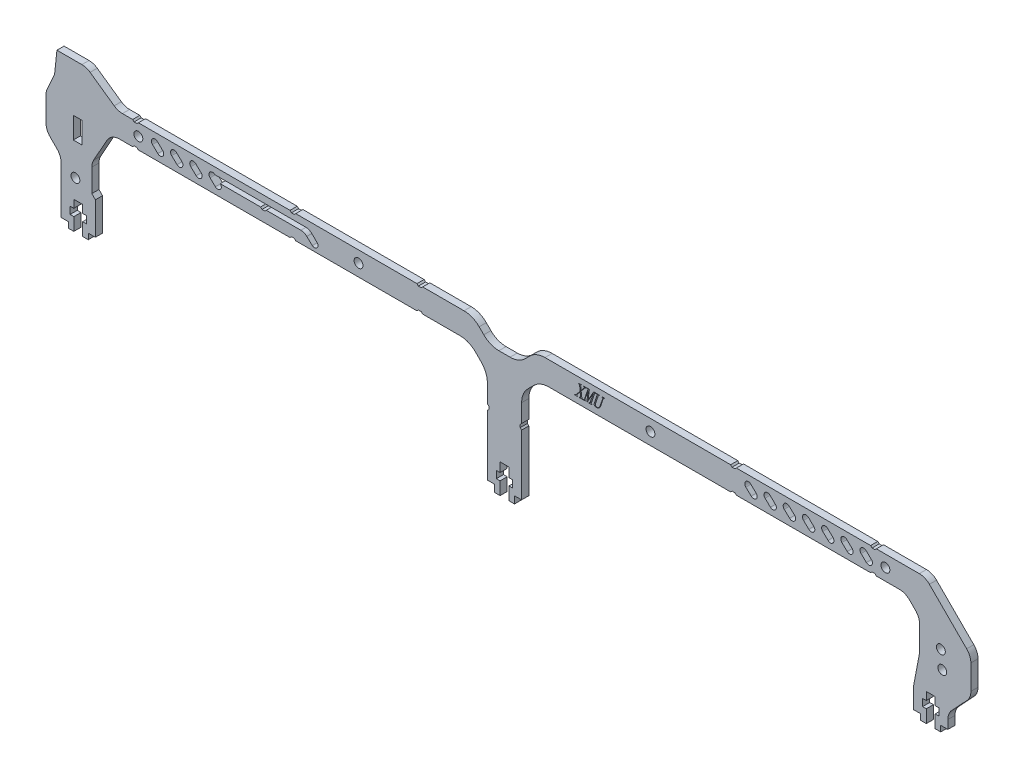
SolidWorks part; units mm, degrees
material "PPS"
ref_plane "前视基准面" through (0, 0, 0) normal (0, 0, 1) x (1, 0, 0)
ref_plane "上视基准面" through (0, 0, 0) normal (0, 1, 0) x (1, 0, 0)
ref_plane "右视基准面" through (0, 0, 0) normal (1, 0, 0) x (0, 0, -1)
sketch "草图1" plane through (0, 0, 0) normal (0, 0, 1) x (1, 0, 0)
  line L0 (-1000, 0) -> (49000, 0) construction
  line L1 (0, 0) -> (0, -218.3822) construction
  line L2 (6, -16.1697) -> (6, -48.75)
  line L3 (6, -48.75) -> (-6, -48.75) construction
  line L4 (-6, -16.1697) -> (-6, -48.75)
  line L5 (6, -48.75) -> (3.5, -48.75)
  line L6 (3.5, -48.75) -> (3.5, -51.25)
  line L7 (3.5, -51.25) -> (-3.5, -51.25) construction
  line L8 (-3.5, -48.75) -> (-3.5, -51.25)
  line L9 (-3.5, -48.75) -> (-6, -48.75)
  line L10 (1.55, -51.25) -> (1.55, -46.75)
  line L11 (1.55, -46.75) -> (2.85, -46.75)
  line L12 (2.85, -46.75) -> (2.85, -44.25)
  line L13 (2.85, -44.25) -> (1.55, -44.25)
  line L14 (1.55, -44.25) -> (1.55, -41)
  line L15 (1.55, -41) -> (-1.55, -41)
  line L16 (-1.55, -44.25) -> (-1.55, -41)
  line L17 (-2.85, -44.25) -> (-1.55, -44.25)
  line L18 (-2.85, -46.75) -> (-2.85, -44.25)
  line L19 (-1.55, -46.75) -> (-2.85, -46.75)
  line L20 (-1.55, -51.25) -> (-1.55, -46.75)
  line L21 (1.55, -51.25) -> (3.5, -51.25)
  line L22 (-1.55, -51.25) -> (-3.5, -51.25)
  line L23 (12.4197, -9.75) -> (6, -16.1697)
  line L24 (-12.4197, -9.75) -> (-6, -16.1697)
  line L25 (-147.7, -45.75) -> (-147.7, -41.25)
  line L26 (-150.8, -45.75) -> (-150.8, -41.25)
  line L27 (-147.7, -41.25) -> (-146.4, -41.25)
  line L28 (-146.4, -41.25) -> (-146.4, -38.75)
  line L29 (-146.4, -38.75) -> (-147.7, -38.75)
  line L30 (-147.7, -38.75) -> (-147.7, -36)
  line L31 (-150.8, -36) -> (-147.7, -36)
  line L32 (-150.8, -38.75) -> (-150.8, -36)
  line L33 (-152.1, -38.75) -> (-150.8, -38.75)
  line L34 (-152.1, -41.25) -> (-152.1, -38.75)
  line L35 (-150.8, -41.25) -> (-152.1, -41.25)
  line L36 (-5.0685, -7.5) -> (5.0685, -7.5)
  line L37 (5.0685, -7.5) -> (11.0685, -1.5)
  line L38 (11.0685, -1.5) -> (147.3211, -1.5)
  line L40 (145.3337, -25.5065) -> (145.3337, -14.709)
  line L41 (140.3747, -9.75) -> (12.4197, -9.75)
  line L42 (-5.0685, -7.5) -> (-11.0685, -1.5)
  line L44 (-11.0685, -1.5) -> (-157.5351, -1.5) construction
  line L45 (-137.7768, -9.75) -> (-12.4197, -9.75)
  line L50 (143.25, -36.4306) -> (143.25, -43.75)
  line L52 (155.25, -43.75) -> (143.25, -43.75) construction
  line L53 (155.25, -43.75) -> (152.75, -43.75)
  line L54 (152.75, -43.75) -> (152.75, -45.75)
  line L55 (152.75, -45.75) -> (145.75, -45.75) construction
  line L56 (145.75, -43.75) -> (145.75, -45.75)
  line L57 (145.75, -43.75) -> (143.25, -43.75)
  line L58 (150.8, -45.75) -> (150.8, -41.25)
  line L59 (150.8, -41.25) -> (152.1, -41.25)
  line L60 (152.1, -41.25) -> (152.1, -38.75)
  line L61 (152.1, -38.75) -> (150.8, -38.75)
  line L62 (150.8, -38.75) -> (150.8, -36)
  line L63 (150.8, -36) -> (147.7, -36)
  line L64 (147.7, -38.75) -> (147.7, -36)
  line L65 (146.4, -38.75) -> (147.7, -38.75)
  line L66 (146.4, -41.25) -> (146.4, -38.75)
  line L67 (147.7, -41.25) -> (146.4, -41.25)
  line L68 (147.7, -45.75) -> (147.7, -41.25)
  line L69 (150.8, -45.75) -> (152.75, -45.75)
  line L70 (147.7, -45.75) -> (145.75, -45.75)
  line L72 (57.6009, -1) -> (44.6221, -1) construction
  line L73 (145.3337, -25.5065) -> (143.25, -36.4306)
  line L74 (-147.7, -45.75) -> (-145.75, -45.75)
  line L75 (-150.8, -45.75) -> (-152.75, -45.75)
  line L76 (-152.75, -43.75) -> (-152.75, -45.75)
  line L77 (-155.25, -43.75) -> (-152.75, -43.75)
  line L78 (-145.75, -43.75) -> (-145.75, -45.75)
  line L79 (-145.75, -43.75) -> (-143.25, -43.75)
  line L80 (-157.5351, -1.5) -> (-160.547, -8.1912)
  line L81 (-160.547, -8.1912) -> (-160.547, -19.809)
  line L82 (-160.547, -19.809) -> (-155.25, -25.0873)
  line L87 (-143.25, -32.3726) -> (-144.5, -31.127)
  line L88 (-144.5, -31.127) -> (-144.5, -21.7902)
  line L89 (-144.5, -21.7902) -> (-137.7768, -9.75)
  line L90 (-155.25, -25.0873) -> (-155.25, -43.75)
  line L91 (-143.25, -32.3726) -> (-143.25, -43.75)
  line L92 (147.3211, -1.5) -> (163.2977, -17.4767)
  line L93 (163.2977, -17.4767) -> (163.2977, -30.1638)
  line L94 (163.2977, -30.1638) -> (155.25, -38.75)
  line L95 (155.25, -38.75) -> (155.25, -43.75)
  line L96 (-157.5351, -1.5) -> (-156.7241, 6.25)
  line L97 (-156.7241, 6.25) -> (-146.4, 6.25)
  line L98 (-146.4, 6.25) -> (-135.37, -1.5)
  line L99 (-135.37, -1.5) -> (-11.0685, -1.5)
  line L102 (140.3747, -9.75) -> (145.3337, -14.709)
  line L103 (56.6009, -9.75) -> (45.6221, -9.75) construction
  line L104 (146.1658, -18.25) -> (92.972, -18.25) construction
  line L105 (-154.7028, -11.25) -> (-130.7962, -11.25) construction
  circle A0 centre (-51.1115, -5.5) radius 1.55
  circle A1 centre (51.1115, -5.5) radius 1.55
  circle A5 centre (-51.1115, -5.5) radius 1.9051 construction
  circle A6 centre (51.1115, -5.5) radius 2.165 construction
  point P6 (0, -48.75)
  point P11 (0, -51.25)
  point P20 (0, -41)
  point P29 (-149.25, -36)
  point P43 (152.75, -44.75)
  point P78 (149.25, -36)
  dimension "D21" = 3.1
  dimension "D1" = 3.5
  dimension "D2" = 4.5
  dimension "D3" = 2.5
  dimension "D4" = 6
  dimension "D5" = 135
  dimension "D6" = 2.5
  dimension "D7" = 48.75
  dimension "D8" = 25.5
  dimension "D9" = 2
  dimension "D10" = 7
  dimension "D11" = 149.25
  dimension "D12" = 1.95
  dimension "D13" = 1.55
  dimension "D14" = 2.85
  dimension "D15" = 10.25
  dimension "D16" = 0.5
  dimension "D17" = 2.25
  dimension "D18" = 135
  dimension "D19" = 135
  dimension "D20" = 1.25
  dimension "D22" = 17.5
extrude "凸台-拉伸1" add sketch "草图1" along normal blind 2.5
sketch "草图2" plane through (0, 0, 0) normal (0, 0, 1) x (1, 0, 0)
  line L0 (98.8244, -4.7341) -> (98.8244, -1.5) construction
  line L2 (147.3211, -1.5) -> (11.0685, -1.5) construction
  line L4 (100.6889, -6.5159) -> (100.6889, -9.75) construction
  line L7 (12.4197, -9.75) -> (140.3747, -9.75) construction
  line L8 (94.8107, -5.6378) -> (97.9607, -5.6378) construction
  line L11 (86.3905, -7.4197) -> (84.526, -5.6378)
  line L16 (121.7047, -5.6122) -> (124.8547, -5.6122) construction
  line L17 (106.5671, -7.394) -> (104.7026, -5.6122)
  line L18 (104.7026, -5.6122) -> (106.4054, -3.8303) construction
  line L19 (106.4054, -3.8303) -> (108.27, -5.6122)
  line L20 (108.27, -5.6122) -> (106.5671, -7.394) construction
  line L21 (99.8252, -7.4197) -> (97.9607, -5.6378)
  line L22 (99.6881, -3.8303) -> (101.5526, -5.6122)
  line L23 (101.5526, -5.6122) -> (104.7026, -5.6122) construction
  line L24 (108.27, -5.6122) -> (111.42, -5.6122) construction
  line L25 (113.2845, -7.394) -> (111.42, -5.6122)
  line L26 (113.1228, -3.8303) -> (114.9873, -5.6122)
  line L27 (114.9873, -5.6122) -> (118.1373, -5.6122) construction
  line L28 (120.0018, -7.394) -> (118.1373, -5.6122)
  line L29 (119.8402, -3.8303) -> (121.7047, -5.6122)
  line L30 (126.7192, -7.394) -> (124.8547, -5.6122)
  line L31 (126.5819, -3.8048) -> (128.4464, -5.5866)
  line L32 (86.2289, -3.856) -> (88.0934, -5.6378)
  line L33 (88.0934, -5.6378) -> (91.2434, -5.6378) construction
  line L34 (93.1079, -7.4197) -> (91.2434, -5.6378)
  line L35 (92.9462, -3.856) -> (94.8107, -5.6378)
  line L36 (-106.2679, -5.6378) -> (-103.1179, -5.6378) construction
  line L38 (-112.9852, -5.6378) -> (-109.8352, -5.6378) construction
  line L39 (-121.4054, -7.4197) -> (-123.27, -5.6378)
  line L42 (-107.9707, -7.4197) -> (-109.8352, -5.6378)
  line L44 (-108.1324, -3.856) -> (-106.2679, -5.6378)
  line L47 (-101.2387, -7.4197) -> (-103.1032, -5.6378)
  line L48 (-101.4003, -3.856) -> (-99.5358, -5.6378) construction
  line L51 (-101.4003, -3.856) -> (-69.6149, -3.856)
  line L56 (-121.5671, -3.856) -> (-119.7026, -5.6378)
  line L57 (-119.7026, -5.6378) -> (-116.5526, -5.6378) construction
  line L58 (-114.6881, -7.4197) -> (-116.5526, -5.6378)
  line L59 (-114.8498, -3.856) -> (-112.9852, -5.6378)
  line L60 (-71.3031, -5.6378) -> (-99.5358, -5.6378)
  line L66 (-67.5422, -4.6871) -> (-65.6228, -6.5214)
  line L69 (-67.311, -8.3033) -> (-69.2304, -6.469)
  arc A10 (126.5819, -3.8048) -> (124.8547, -5.6122) centre (125.7183, -4.7085) ccw
  arc A11 (128.4464, -5.5866) -> (126.7192, -7.394) centre (127.5828, -6.4903) cw
  arc A12 (106.4054, -3.8303) -> (104.7026, -5.6122) centre (105.554, -4.7213) ccw
  arc A13 (108.27, -5.6122) -> (106.5671, -7.394) centre (107.4185, -6.5031) cw
  arc A14 (99.6881, -3.8303) -> (97.9607, -5.6378) centre (98.8244, -4.7341) ccw
  arc A15 (101.5526, -5.6122) -> (99.8252, -7.4197) centre (100.6889, -6.5159) cw
  arc A16 (113.1228, -3.8303) -> (111.42, -5.6122) centre (112.2714, -4.7213) ccw
  arc A17 (114.9873, -5.6122) -> (113.2845, -7.394) centre (114.1359, -6.5031) cw
  arc A18 (119.8402, -3.8303) -> (118.1373, -5.6122) centre (118.9887, -4.7213) ccw
  arc A19 (121.7047, -5.6122) -> (120.0018, -7.394) centre (120.8532, -6.5031) cw
  arc A20 (86.2289, -3.856) -> (84.526, -5.6378) centre (85.3774, -4.7469) ccw
  arc A21 (88.0934, -5.6378) -> (86.3905, -7.4197) centre (87.242, -6.5287) cw
  arc A22 (92.9462, -3.856) -> (91.2434, -5.6378) centre (92.0948, -4.7469) ccw
  arc A23 (94.8107, -5.6378) -> (93.1079, -7.4197) centre (93.9593, -6.5287) cw
  arc A34 (-121.5671, -3.856) -> (-123.27, -5.6378) centre (-122.4185, -4.7469) ccw
  arc A35 (-119.7026, -5.6378) -> (-121.4054, -7.4197) centre (-120.554, -6.5287) cw
  arc A36 (-114.8498, -3.856) -> (-116.5526, -5.6378) centre (-115.7012, -4.7469) ccw
  arc A37 (-112.9852, -5.6378) -> (-114.6881, -7.4197) centre (-113.8367, -6.5287) cw
  arc A38 (-108.1324, -3.856) -> (-109.8352, -5.6378) centre (-108.9838, -4.7469) ccw
  arc A39 (-106.2679, -5.6378) -> (-107.9707, -7.4197) centre (-107.1193, -6.5287) cw
  arc A40 (-101.4003, -3.856) -> (-103.1032, -5.6378) centre (-102.2518, -4.7469) ccw
  arc A41 (-99.5358, -5.6378) -> (-101.2387, -7.4197) centre (-100.3873, -6.5287) cw
  arc A46 (-71.3031, -5.6378) -> (-69.2304, -6.469) centre (-71.3031, -8.6378) cw
  arc A47 (-65.6228, -6.5214) -> (-67.311, -8.3033) centre (-66.548, -7.3355) cw
  arc A48 (-69.6149, -3.856) -> (-67.5422, -4.6871) centre (-69.6149, -6.856) cw
extrude "减重" cut sketch "草图2" against normal through all from surface starting at face at (-5.419, -33.6883, 2.5)
sketch "草图5" plane through (0, 0, 0) normal (0, 0, 1) x (1, 0, 0)
  line L0 (-123.27, -5.6378) -> (-121.4054, -7.4197) construction
  line L1 (-126.42, -5.6378) -> (-123.27, -5.6378) construction
  line L2 (-126.42, -5.6378) -> (-128.2845, -3.856) construction
  line L3 (-128.1228, -7.4197) -> (-129.9873, -5.6378) construction
  line L4 (-129.1359, -4.7469) -> (-127.2714, -6.5287) construction
  line L5 (132.4479, -4.6957) -> (134.3124, -6.4776) construction
  line L9 (128.4464, -5.5866) -> (131.5964, -5.5866) construction
  line L10 (135.1638, -5.5866) -> (133.2993, -3.8048) construction
  line L11 (133.4609, -7.3685) -> (131.5964, -5.5866) construction
  arc A1 (-126.42, -5.6378) -> (-128.1228, -7.4197) centre (-127.2714, -6.5287) cw construction
  arc A2 (-129.9873, -5.6378) -> (-128.2845, -3.856) centre (-129.1359, -4.7469) cw construction
  arc A7 (135.1638, -5.5866) -> (133.4609, -7.3685) centre (134.3124, -6.4776) cw construction
  arc A8 (131.5964, -5.5866) -> (133.2993, -3.8048) centre (132.4479, -4.6957) cw construction
  circle A9 centre (-128.2036, -5.6378) radius 1.55
  circle A11 centre (133.3801, -5.5866) radius 1.55
  dimension "D1" = 3.1
extrude "光球接口" cut sketch "草图5" along normal through all
sketch "草图3" plane through (0, 0, 2.5) normal (0, 0, 1) x (1, 0, 0)
  text T0 "XMU" font "宋体" height 4.25
extrude "切除-拉伸3" cut sketch "草图3" against normal through all
sketch "草图4" plane through (0, 0, 0) normal (0, 0, 1) x (1, 0, 0)
  line L0 (-6, -25.591) -> (-5.5, -26.091)
  line L1 (-6, -16.1697) -> (-6, -48.75) construction
  line L2 (-5.5, -26.091) -> (-5.5, -27.091)
  line L3 (-5.5, -27.091) -> (-6, -27.591)
  line L4 (-6, -27.591) -> (-6, -25.591)
  line L5 (0, 0) -> (0, -67.6388) construction
  line L6 (6, -27.591) -> (6, -25.591)
  line L7 (5.5, -27.091) -> (6, -27.591)
  line L8 (5.5, -26.091) -> (5.5, -27.091)
  line L9 (6, -25.591) -> (5.5, -26.091)
  line L18 (-11.0685, -1.5) -> (-135.37, -1.5) construction
  line L19 (-128.2051, -1.5) -> (-130.2051, -1.5)
  line L20 (-128.7051, -2) -> (-128.2051, -1.5)
  line L21 (-129.7051, -2) -> (-128.7051, -2)
  line L22 (-130.2051, -1.5) -> (-129.7051, -2)
  line L23 (0, 0) -> (-134.5835, 0) construction
  line L36 (-137.7768, -9.75) -> (-12.4197, -9.75) construction
  line L41 (-99.5358, -5.6378) -> (-71.3031, -5.6378) construction
  line L46 (130.2051, -1.5) -> (129.7051, -2)
  line L47 (129.7051, -2) -> (128.7051, -2)
  line L48 (128.7051, -2) -> (128.2051, -1.5)
  line L49 (128.2051, -1.5) -> (130.2051, -1.5)
  line L50 (-135.37, -1.5) -> (-135.37, -9.75) construction
  line L51 (-1135.37, -5.625) -> (48864.63, -5.625) construction
  line L52 (-130.2051, -9.75) -> (-129.7051, -9.25)
  line L53 (-129.7051, -9.25) -> (-128.7051, -9.25)
  line L54 (-128.7051, -9.25) -> (-128.2051, -9.75)
  line L55 (-128.2051, -9.75) -> (-130.2051, -9.75)
  line L64 (-73.0982, -1.5) -> (-75.0982, -1.5)
  line L65 (-73.5982, -2) -> (-73.0982, -1.5)
  line L66 (-74.5982, -2) -> (-73.5982, -2)
  line L67 (-75.0982, -1.5) -> (-74.5982, -2)
  line L68 (-75.0982, -9.75) -> (-74.5982, -9.25)
  line L69 (-74.5982, -9.25) -> (-73.5982, -9.25)
  line L70 (-73.5982, -9.25) -> (-73.0982, -9.75)
  line L71 (-73.0982, -9.75) -> (-75.0982, -9.75)
  line L72 (-28.6523, -1.5) -> (-30.6523, -1.5)
  line L73 (-29.1523, -2) -> (-28.6523, -1.5)
  line L74 (-30.1523, -2) -> (-29.1523, -2)
  line L75 (-30.6523, -1.5) -> (-30.1523, -2)
  line L76 (-30.6523, -9.75) -> (-30.1523, -9.25)
  line L77 (-30.1523, -9.25) -> (-29.1523, -9.25)
  line L78 (-29.1523, -9.25) -> (-28.6523, -9.75)
  line L79 (-28.6523, -9.75) -> (-30.6523, -9.75)
  line L80 (-83.4194, -5.6378) -> (-85.4194, -5.6378)
  line L81 (-83.9194, -6.1378) -> (-83.4194, -5.6378)
  line L82 (-84.9194, -6.1378) -> (-83.9194, -6.1378)
  line L83 (-85.4194, -5.6378) -> (-84.9194, -6.1378)
  line L92 (79.1823, -9.75) -> (81.1823, -9.75)
  line L93 (128.2051, -9.75) -> (130.2051, -9.75)
  line L94 (128.7051, -9.25) -> (128.2051, -9.75)
  line L95 (129.7051, -9.25) -> (128.7051, -9.25)
  line L96 (130.2051, -9.75) -> (129.7051, -9.25)
  line L97 (-151, -10.625) -> (-148, -10.625)
  line L98 (-148, -10.625) -> (-148, -18.125)
  line L99 (-148, -18.125) -> (-151, -18.125)
  line L100 (-151, -18.125) -> (-151, -10.625)
  line L101 (79.6823, -9.25) -> (79.1823, -9.75)
  line L102 (80.6823, -9.25) -> (79.6823, -9.25)
  line L103 (81.1823, -9.75) -> (80.6823, -9.25)
  line L104 (81.1823, -1.5) -> (80.6823, -2)
  line L105 (80.6823, -2) -> (79.6823, -2)
  line L106 (79.6823, -2) -> (79.1948, -1.5)
  line L107 (79.1948, -1.5) -> (81.1823, -1.5)
  line L108 (147.3211, -1.5) -> (11.0685, -1.5) construction
  line L109 (163.2977, -30.1638) -> (163.2977, -17.4767) construction
  line L110 (-144.5, -31.127) -> (-144.5, -21.7902) construction
  line L112 (-155.25, -43.75) -> (-152.75, -43.75) construction
  circle A0 centre (-150.25, -29.25) radius 1.55
  circle A1 centre (152.7976, -20.675) radius 1.55
  circle A2 centre (153.2976, -26.6541) radius 1.55
  point P4 (-6, -26.591)
  point P19 (-85.4194, -5.6378)
  point P49 (-135.37, -5.625)
  dimension "D13" = 3.1
  dimension "D20" = 3.1
  dimension "D1" = 45
  dimension "D2" = 0.5
  dimension "D3" = 1
  dimension "D4" = 45
  dimension "D5" = 0.5
  dimension "D6" = 1
  dimension "D7" = 45
  dimension "D8" = 1
  dimension "D9" = 6
  dimension "D10" = 15.05
  dimension "D11" = 10.0002
  dimension "D12" = 0.5
  dimension "D14" = 5
  dimension "D15" = 7.5
  dimension "D16" = 3
  dimension "D17" = 14.5
  dimension "D18" = 3.5
  dimension "D19" = 5.75
extrude "线槽和设备接口" cut sketch "草图4" along normal through all
fillet "圆角2" radius 5 16 edges at (155.25, -38.75, 1.25) (145.3337, -25.5065, 1.25) (143.25, -36.4306, 1.25) (147.3211, -1.5, 1.25) (163.2977, -30.1638, 1.25) (163.2977, -17.4767, 1.25) (145.3337, -14.709, 1.25) (140.3747, -9.75, 1.25) (-137.7768, -9.75, 1.25) (-144.5, -21.7902, 1.25) (-146.4, 6.25, 1.25) (-155.25, -25.0873, 1.25) (-160.547, -19.809, 1.25) (-160.547, -8.1912, 1.25) (-157.5351, -1.5, 1.25) (-135.37, -1.5, 1.25)
fillet "圆角3" radius 7.5 8 edges at (12.4197, -9.75, 1.25) (6, -16.1697, 1.25) (-6, -16.1697, 1.25) (-12.4197, -9.75, 1.25) (11.0685, -1.5, 1.25) (5.0685, -7.5, 1.25) (-5.0685, -7.5, 1.25) (-11.0685, -1.5, 1.25)
